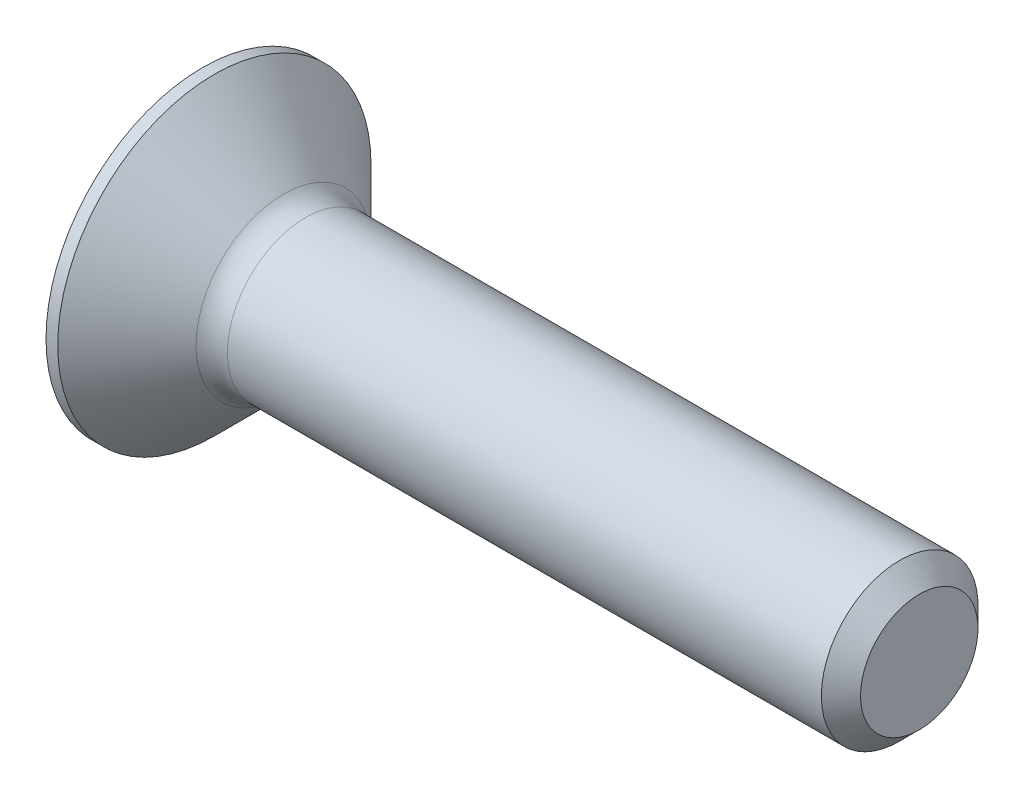
SolidWorks part; units mm, degrees
note: '?' marks a value the reader was unsure of.
revolve "PreBroach" cut sketch "Sketch2"
sketch "Sketch2"
  line L0 (0, 1.25) -> (3.5, 1.25)
  line L1 (3.5, 1.25) -> (4.2217, 0)
  line L2 (0, 0) -> (127, 0) construction
  line L3 (4.2217, 0) -> (0, 0)
  line L4 (0, 0) -> (0, 1.25)
  line L5 (0, -1.25) -> (3.5, -1.25) construction
  line L6 (0, 0) -> (47.625, 0) construction
  line L8 (0, 4) -> (0, -4) construction
  dimension "D2" = 60
revolve "BaseBody" add sketch "BodySke" angle 360 about L6
sketch "BodySke" plane through (0, 0, 0) normal (0, 0, 1) x (1, 0, 0)
  line L0 (0, 0) -> (0, 4)
  line L1 (0.3, 4) -> (2.3, 2)
  line L2 (0, 4) -> (0.3, 4)
  line L3 (2.3, 2) -> (17.8, 2)
  line L4 (18.3, 1.5) -> (18.3, 0)
  line L5 (18.3, 0) -> (0, 0)
  line L6 (0, 0) -> (127, 0) construction
  line L7 (0.3, -4) -> (2.3, -2) construction
  line L8 (18.3, 1.5) -> (17.8, 2)
  line L9 (0, -4) -> (0.3, -4) construction
  line L10 (18.3, -1.5) -> (17.8, -2) construction
  line L11 (3.1198, 12.35) -> (3.1198, -9.875) construction
  line L12 (5, 19.05) -> (5, -3.175) construction
  dimension "Diameter" = 4
  dimension "Head_dia" = 8
  dimension "D2" = 16
  dimension "D1" = 2.3
cosmetic thread "ThreadCosmetic"
ref_plane "Plane1" through (0, 0, 0) normal (0, 0, 1) x (1, 0, 0)
ref_plane "Plane2" through (0, 0, 0) normal (0, 1, 0) x (1, 0, 0)
ref_plane "Plane3" through (0, 0, 0) normal (1, 0, 0) x (0, 0, -1)
fillet "Fillet1" radius 0.8 1 edges at (2.3, 0, 2)
sketch "Sketch3" plane through (0, 0, 0) normal (-1, 0, 0) x (0, 0, 1)
  line L0 (-1.25, -0.7217) -> (-1.25, 0.7217)
  line L1 (-1.25, 0.7217) -> (0, 1.4434)
  line L2 (0, 1.4434) -> (1.25, 0.7217)
  line L3 (1.25, 0.7217) -> (1.25, -0.7217)
  line L4 (1.25, -0.7217) -> (0, -1.4434)
  line L5 (0, -1.4434) -> (-1.25, -0.7217)
  dimension "Hex_size" = 2.5
  dimension "D1" = 1.25
  dimension "D2" = 1.25
  dimension "D3" = 2.5
extrude "Hex" cut sketch "Sketch3" against normal blind 5.6
sketch "ThdSchSke" plane through (0, 0, 0) normal (0, 0, 1) x (1, 0, 0)
  line L0 (17.66, -1.5) -> (17.3099, -2)
  line L1 (17.66, -1.5) -> (18.0101, -2)
  line L2 (18.0101, -2) -> (18.0101, -2.5)
  line L3 (-3.175, 0) -> (5.1513, 0) construction
  line L4 (0, 4) -> (0, -4) construction
  line L5 (18.0101, -2.5) -> (17.3099, -2.5)
  line L6 (17.3099, -2.5) -> (17.3099, -2)
  dimension "Diameter" = 4
  dimension "Thread_minor" = 3
  dimension "Start" = 17.66
revolve "ThreadSchematic" [suppressed] cut sketch "ThdSchSke" angle 360 about L3
pattern_linear "ThdSchPat" [suppressed]
sketch "Эскиз2" plane through (18.3, 0, 0) normal (1, 0, 0) x (0, 0, -1)
  line L0 (-3, 3.633) -> (-3, -3.3586) construction
  line L1 (-10.7916, 20) -> (11.2892, 20) construction
  line L2 (-10.7916, -20) -> (11.2892, -20) construction
  point P0 (0, 0)
  point P8 (0, 0)
  dimension "D1" = 3
  dimension "D2" = 20
  dimension "D3" = 20
sketch "Эскиз3" plane through (0, 0, 0) normal (-1, 0, 0) x (0, 0, 1)
  line L0 (3, -3.3586) -> (3, 3.633) construction
  line L1 (-11.2892, -20) -> (10.7916, -20) construction
  line L2 (-11.2892, 20) -> (10.7916, 20) construction
  point P12 (0, 0)
ref_plane "кромка" through (0, 0, 3) normal (0, 0, -1) x (-1, 0, 0)
ref_plane "край" through (0, 20, 0) normal (0, 1, 0) x (1, 0, 0)
ref_plane "край2" through (0, -20, 0) normal (0, 1, 0) x (1, 0, 0)
ref_axis "Ось1" through (18.3, 0, 0) along (-1, 0, 0)?
equation "\"Thread_minor@ThreadCosmetic\"  =  \"Minor_dia@BodySke\""
equation "\"D1@Sketch3\" = \"Hex_size@Sketch3\" / 2"
equation "\"D2@Sketch3\" = \"D1@Sketch3\""
equation "\"D3@Sketch3\" = \"Hex_size@Sketch3\""
equation "\"Thread_length@ThreadCosmetic\" =  (  ( sgn (  ( \"Length@BodySke\" - \"Advance@BodySke\" *  3.0  - \"Head_ht@BodySke\" )  - \"Thread_nom@BodySke\" )  - 1 )  *  (  ( \"Length@BodySke\" - \"Advance@BodySke\" *  3.0  - \"Head_ht@BodySke\" )  - \"Thread_nom@BodySke\" )  )  /  - 2 + \"Thread_nom@BodySke\""
equation "\"Thread_minor@ThdSchSke\" = \"Minor_dia@BodySke\""
equation "\"Diameter@ThdSchSke\" = \"Diameter@BodySke\""
equation "\"Overcut@ThdSchSke\" = \"Diameter@BodySke\" * 1.25"
equation "\"Num_threads@ThdSchPat\" =  int ( \"Thread_length@ThreadCosmetic\" / \"Advance@BodySke\" +  0.999  )  +  1"
equation "\"Num_threads@ThdSchPat\" = \"Num_threads@ThdSchPat\" - sgn( \"Num_threads@ThdSchPat\" - 1) '---chamfered tips only---"
equation "\"D3@Эскиз2\"=\"D2@Эскиз2\""
